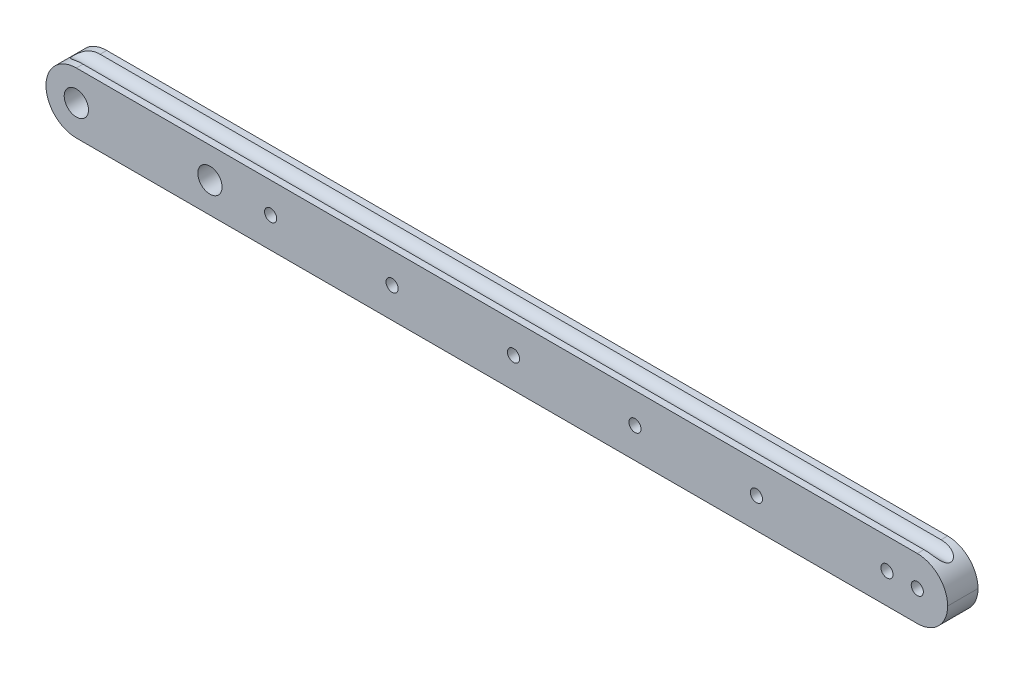
SolidWorks part; units mm, degrees
material "AISI 316 Barre d'acier inoxydable recuit (SS)"
ref_plane "Plan de face" through (0, 0, 0) normal (0, 0, 1) x (1, 0, 0)
ref_plane "Plan de dessus" through (0, 0, 0) normal (0, 1, 0) x (1, 0, 0)
ref_plane "Plan de droite" through (0, 0, 0) normal (1, 0, 0) x (0, 0, -1)
sketch "Esquisse1" plane through (0, 0, 0) normal (0, 0, 1) x (1, 0, 0)
  line L0 (0, 10) -> (297, 10) construction
  line L1 (0, 20) -> (297, 20) construction
  line L2 (0, 20) -> (0, 0)
  line L3 (0, 0) -> (297, 0) construction
  line L4 (297, 20) -> (297, 0)
  line L5 (148.5, 20) -> (148.5, 0) construction
  line L6 (0, 20) -> (60, 20)
  line L7 (297, 20) -> (277, 20)
  line L8 (60, 20) -> (277, 20)
  line L9 (81.7, 18) -> (88.9319, 18) construction
  line L10 (297, 0) -> (277, 0)
  line L11 (0, 0) -> (60, 0)
  line L12 (81.7, 2) -> (88.9319, 2) construction
  line L13 (277, 0) -> (60, 0)
  circle A0 centre (10, 10) radius 4
  circle A1 centre (54, 10) radius 4
  circle A2 centre (277, 10) radius 2
  circle A3 centre (287, 10) radius 2
  circle A4 centre (74, 10) radius 2
  circle A36 centre (114, 10) radius 2
  circle A37 centre (154, 10) radius 2
  circle A38 centre (194, 10) radius 2
  circle A39 centre (234, 10) radius 2
  dimension "D3" = 8
  dimension "D4" = 44
  dimension "D7" = 4
  dimension "D9" = 20
  dimension "D10" = 4
  dimension "D11" = 5
  dimension "D12" = 20
  dimension "D13" = 60
  dimension "D14" = 40
  dimension "D1" = 20
  dimension "D2" = 297
  dimension "D5" = 10
  dimension "D6" = 10
  dimension "D8" = 10
  dimension "D17" = 2
extrude "Boss.-Extru.1" add sketch "Esquisse1" along normal blind 10
fillet "Congé1" radius 10 4 edges at (0, 0, 5) (0, 20, 5) (297, 0, 5) (297, 20, 5)
sketch "Esquisse2" plane through (0, 0, 0) normal (1, 0, 0) x (0, 0, -1)
  line L0 (-10, 10) -> (0, 10) construction
  line L3 (-10, 20) -> (0, 20) construction
  line L4 (-5, 10) -> (-5, 21) construction
  circle A0 centre (-5, 21) radius 3
  dimension "D1" = 6
  dimension "D2" = 1
extrude "Enlèv. mat.-Extru.2" cut sketch "Esquisse2" along normal through all and the other way through all from offset 70
